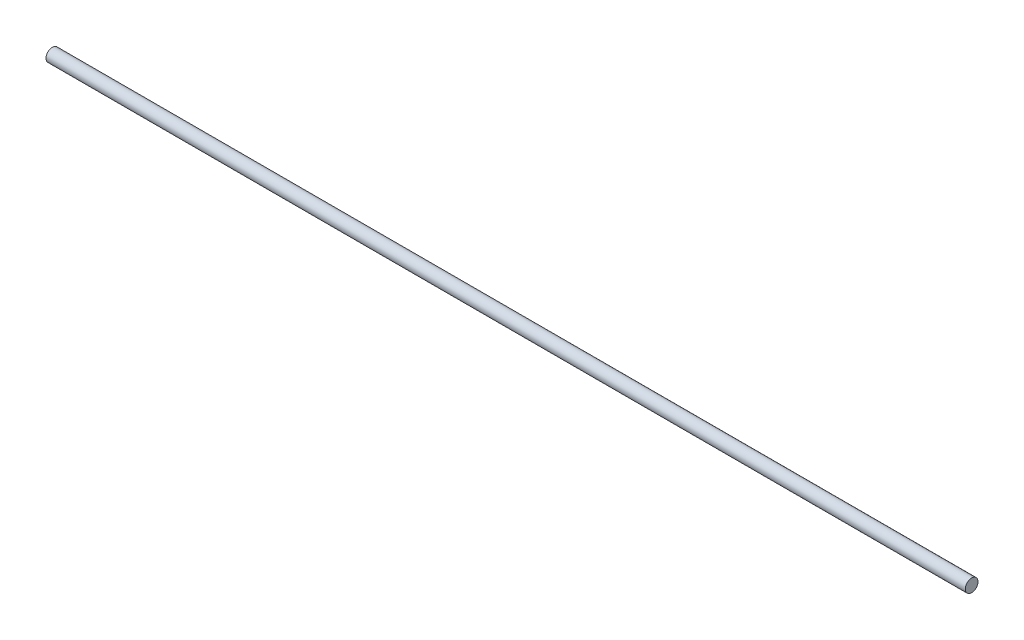
SolidWorks part; units mm, degrees
material "Cast Stainless Steel"
ref_plane "Front" through (0, 0, 0) normal (0, 0, 1) x (1, 0, 0)
ref_plane "Top" through (0, 0, 0) normal (0, 1, 0) x (1, 0, 0)
ref_plane "Right" through (0, 0, 0) normal (1, 0, 0) x (0, 0, -1)
sketch "Sketch1" plane through (0, 0, 0) normal (1, 0, 0) x (0, 0, -1)
  circle A0 centre (0, 0) radius 6.35
  dimension "D1" = 12.7
extrude "Boss-Extrude1" add sketch "Sketch1" along normal blind 914.4
